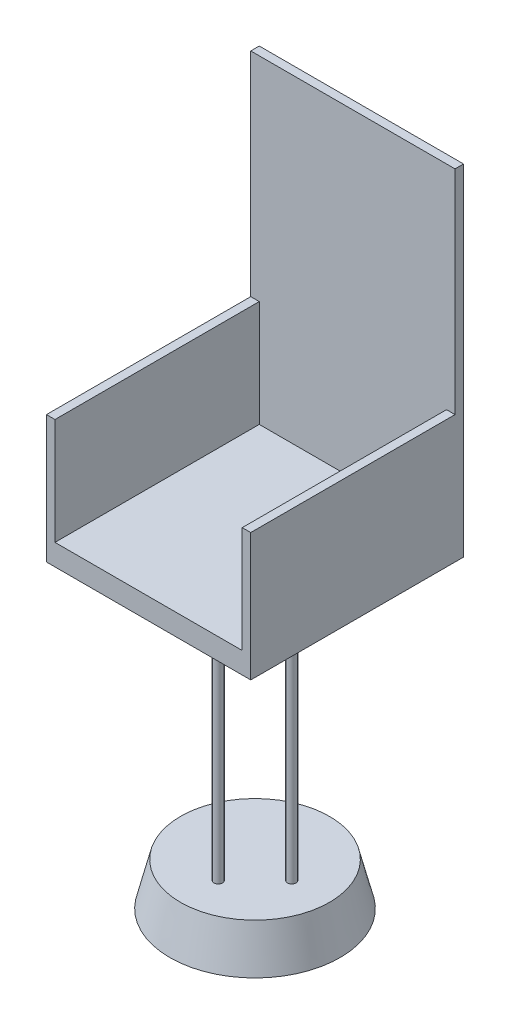
SolidWorks part; units mm, degrees
ref_plane "Front Plane" through (0, 0, 0) normal (0, 0, 1) x (1, 0, 0)
ref_plane "Top Plane" through (0, 0, 0) normal (0, 1, 0) x (1, 0, 0)
ref_plane "Right Plane" through (0, 0, 0) normal (1, 0, 0) x (0, 0, -1)
sketch "Sketch1" plane through (0, 0, 0) normal (0, 1, 0) x (1, 0, 0)
  circle A0 centre (0, 0) radius 200
extrude "Boss-Extrude1" add sketch "Sketch1" along normal blind 100 draft 14 contours A0
sketch "Sketch2" plane through (0, 100, 0) normal (0, 1, 0) x (1, 0, 0)
  circle A1 centre (86.3448, 0) radius 10
  circle A2 centre (0, -86.3448) radius 10
  circle A3 centre (-86.3448, 0) radius 10
  circle A4 centre (0, 86.3448) radius 10
  dimension "D1" = 4
extrude "Boss-Extrude2" add sketch "Sketch2" along normal blind 610
sketch "Sketch7" plane through (0, 710, 0) normal (0, 1, 0) x (1, 0, 0)
  line L1 (-240, 250) -> (240, 250)
  line L2 (-240, 250) -> (-240, -250)
  line L3 (-240, -250) -> (240, -250)
  line L4 (240, 250) -> (240, -250)
  line L5 (-240, 250) -> (240, -250) construction
  line L6 (-240, -250) -> (240, 250) construction
  point P0 (0, 0)
  dimension "D1" = 480
  dimension "D2" = 500
extrude "Boss-Extrude8" add sketch "Sketch7" along normal blind 50
sketch "Sketch8" plane through (0, 760, 0) normal (0, 1, 0) x (1, 0, 0)
  line L0 (240, -250) -> (240, 250) construction
  line L1 (-240, 250) -> (240, 250)
  line L2 (-240, 250) -> (-240, 230)
  line L3 (-240, 230) -> (240, 230)
  line L4 (240, 250) -> (240, 230)
  dimension "D1" = 20
extrude "Boss-Extrude9" add sketch "Sketch8" along normal blind 750
sketch "Sketch9" plane through (0, 760, 0) normal (0, 1, 0) x (1, 0, 0)
  line L0 (-240, -250) -> (240, -250) construction
  line L1 (-240, 230) -> (-220, 230)
  line L2 (-240, 230) -> (-240, -250)
  line L3 (-240, -250) -> (-220, -250)
  line L4 (-220, 230) -> (-220, -250)
  line L6 (240, 230) -> (220, 230)
  line L7 (240, 230) -> (240, -250)
  line L8 (240, -250) -> (220, -250)
  line L9 (220, 230) -> (220, -250)
  dimension "D1" = 20
  dimension "D2" = 20
extrude "Boss-Extrude10" add sketch "Sketch9" along normal blind 250
